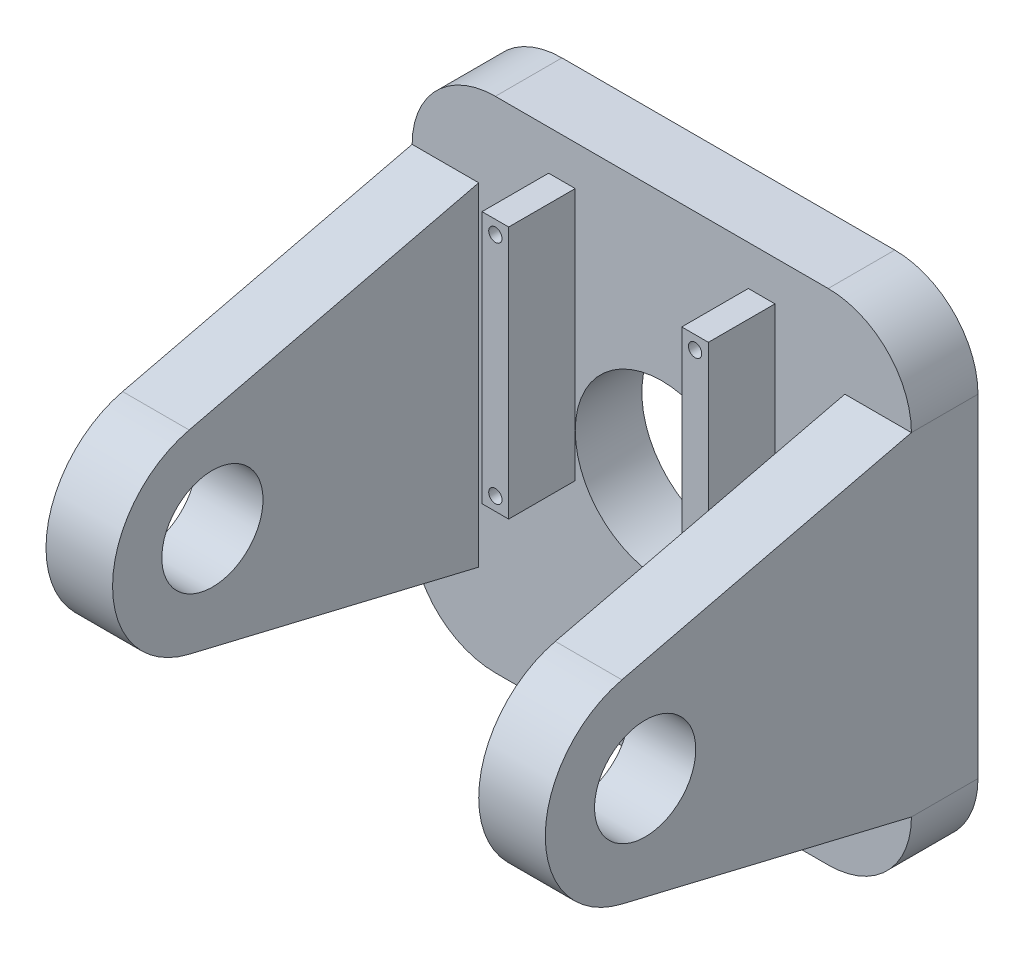
SolidWorks part; units mm, degrees
ref_plane "Front Plane" through (0, 0, 0) normal (1, 0, 0) x (0, 1, 0)
ref_plane "Top Plane" through (0, 0, 0) normal (0, 0, 1) x (0, 1, 0)
ref_plane "Right Plane" through (0, 0, 0) normal (0, 1, 0) x (-1, 0, 0)
sketch "Sketch1" plane through (0, 0, 0) normal (0, 0, 1) x (0, 1, 0)
  line L1 (-25, -37.5) -> (25, -37.5)
  line L2 (-37.5, -25) -> (-37.5, 25)
  line L3 (-25, 37.5) -> (25, 37.5)
  line L4 (37.5, -25) -> (37.5, 25)
  line L5 (-37.5, -37.5) -> (37.5, 37.5) construction
  line L6 (-37.5, 37.5) -> (37.5, -37.5) construction
  arc A0 (-25, -37.5) -> (-37.5, -25) centre (-25, -25) cw
  arc A1 (25, -37.5) -> (37.5, -25) centre (25, -25) ccw
  arc A2 (25, 37.5) -> (37.5, 25) centre (25, 25) cw
  arc A3 (-37.5, 25) -> (-25, 37.5) centre (-25, 25) cw
  point P0 (0, 0)
  dimension "D2" = 12.5
  dimension "D1" = 75
extrude "Boss-Extrude1" add sketch "Sketch1" along normal blind 10
sketch "Sketch2" plane through (37.5, 0, 0) normal (1, 0, 0) x (0, 1, 0)
  line L0 (0, 50) -> (0, 0) construction
  line L1 (-25, 10) -> (25, 10) construction
  line L2 (-25, 10) -> (-14.5878, 53.4924)
  line L3 (25, 10) -> (14.5878, 53.4924)
  line L4 (25, 10) -> (25, 0) construction
  line L5 (37.5, 10) -> (25, 10) construction
  circle A0 centre (0, 50) radius 15
  circle A1 centre (0, 50) radius 7.6
  line M8 (25, 10) -> (-25, 10)
  dimension "D2" = 30
  dimension "D3" = 15.2
  dimension "D1" = 40
extrude "Boss-Extrude2" add sketch "Sketch2" against normal blind 10 contours L0 A0 L2 M8 | A0 L0 L3 M8 | A1 A0 region at (37.5, -11.4437, 40.9726) region at (37.5, 11.3969, 24.1864) region at (37.5, -11.3969, 24.1864)
mirror "Mirror1" about plane through (0, 0, 0) normal (1, 0, 0) of "Boss-Extrude2"
sketch "Sketch3" plane through (0, 0, 10) normal (0, 0, 1) x (1, 0, 0)
  line L0 (0, 37.5) -> (0, -37.5) construction
  line L1 (25, 37.5) -> (-25, 37.5) construction
  line L2 (-25, -37.5) -> (25, -37.5) construction
  circle A0 centre (0, 32.5) radius 1.6
  circle A1 centre (0, -32.5) radius 1.6
  dimension "D1" = 3.2
  dimension "D2" = 5
  dimension "D3" = 5
extrude "Cut-Extrude1" [suppressed] cut sketch "Sketch3" against normal through all
sketch "Sketch4" plane through (0, 0, 10) normal (0, 0, 1) x (1, 0, 0)
  circle A0 centre (0, 0) radius 13
  dimension "D1" = 26
extrude "Cut-Extrude2" cut sketch "Sketch4" against normal through all
sketch "Sketch5" plane through (0, 0, 10) normal (0, 0, 1) x (1, 0, 0)
  line L1 (-17, 31.5) -> (17, 31.5)
  line L2 (-17, 31.5) -> (-17, -6.5)
  line L3 (-17, -6.5) -> (17, -6.5)
  line L4 (17, 31.5) -> (17, -6.5)
  line L5 (-17, 31.5) -> (17, -6.5) construction
  line L6 (-17, -6.5) -> (17, 31.5) construction
  line L7 (-13, -6.5) -> (13, -6.5)
  line L8 (-13, -6.5) -> (-13, 31.5)
  line L9 (-13, 31.5) -> (13, 31.5)
  line L10 (13, -6.5) -> (13, 31.5)
  line L11 (-13, -6.5) -> (13, 31.5) construction
  line L12 (-13, 31.5) -> (13, -6.5) construction
  circle A0 centre (15, -4.5) radius 1
  circle A1 centre (-15, -4.5) radius 1
  circle A2 centre (-15, 29.5) radius 1
  circle A3 centre (15, 29.5) radius 1
  point P12 (0, 12.5)
  point P17 (0, 12.5)
  dimension "D1" = 2
  dimension "D3" = 2
  dimension "D5" = 2
  dimension "D2" = 2
  dimension "D4" = 2
  dimension "D7" = 4
extrude "Boss-Extrude3" add sketch "Sketch5" along normal blind 10 contours L3 L8 L1 L2 A2 A1 | L10 L3 L4 L1 A3 A0 region at (-15, 12.5, 10) region at (15, 12.5, 10)
